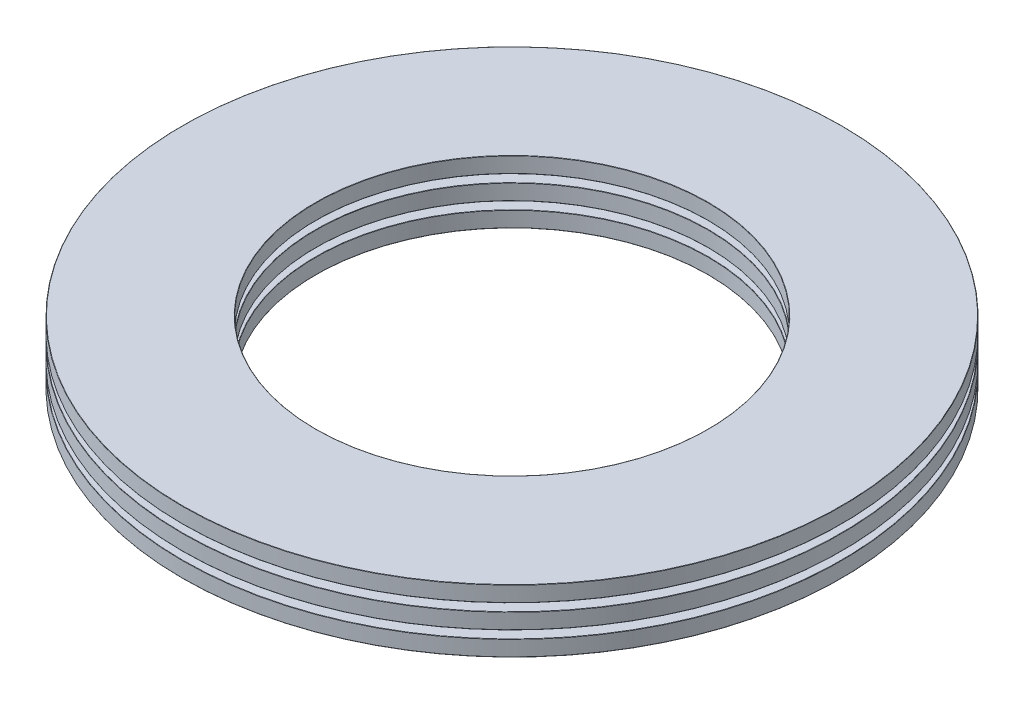
SolidWorks part; units mm, degrees
material "Alloy Steel"
ref_plane "Front Plane" through (0, 0, 0) normal (0, 0, 1) x (1, 0, 0)
ref_plane "Top Plane" through (0, 0, 0) normal (0, 1, 0) x (1, 0, 0)
ref_plane "Right Plane" through (0, 0, 0) normal (1, 0, 0) x (0, 0, -1)
sketch "Sketch1" plane through (0, 0, 0) normal (1, 0, 0) x (0, 0, -1)
  line L0 (-21, 0) -> (21, 0) construction
  line L1 (0, -1) -> (0, 1) construction
  line L2 (-21, 0.5) -> (-12.5, 0.5)
  line L3 (-21, 0.5) -> (-21, -0.5)
  line L4 (-21, -0.5) -> (-12.5, -0.5)
  line L5 (-12.5, 0.5) -> (-12.5, -0.5)
  line L7 (-16.75, 1) -> (-16.75, 0.5) construction
  line L8 (-19.9375, 1) -> (-13.5625, 1) construction
  line L9 (-19.9375, 1) -> (-19.9375, -1) construction
  line L10 (-19.9375, -1) -> (-13.5625, -1) construction
  line L11 (-13.5625, 1) -> (-13.5625, -1) construction
  point P16 (-19.9375, 0)
  dimension "D1" = 6.375
  dimension "OD" = 42
  dimension "Shaft Dia" = 25
  dimension "Th" = 2
  dimension "D2" = 1
  dimension "D3" = 8.5
revolve "Revolve1" add sketch "Sketch1" angle 360 about L1
sketch "Sketch3" plane through (0, 0, 0) normal (1, 0, 0) x (0, 0, -1)
  line L0 (-19.9375, 1) -> (-19.9375, -1) construction
  line L1 (-19.9375, 0) -> (-13.5625, 0)
  line L2 (-19.9375, 0) -> (-19.9375, 1)
  line L3 (-19.9375, 1) -> (-13.5625, 1)
  line L4 (-13.5625, 0) -> (-13.5625, 1)
revolve "Cut-Revolve1" cut sketch "Sketch3" angle 360 about L1
sketch "Sketch2" plane through (0, 0, 0) normal (1, 0, 0) x (0, 0, -1)
  line L1 (-19.9375, 0) -> (-13.5625, 0)
  line L2 (-19.9375, 0) -> (-19.9375, 1)
  line L3 (-19.9375, 1) -> (-13.5625, 1)
  line L4 (-13.5625, 0) -> (-13.5625, 1)
revolve "Revolve2" add sketch "Sketch2" angle 360 about L1
ref_axis "Axis1" through (0, 1, 0) along (0, -1, 0)
pattern_circular "CirPattern1" count 16 over 360 about axis through (0, 1, 0) along (0, -1, 0) of bodies 187 411
pattern_circular "CirPattern2" count 16 every 22.5 about axis through (0, 1, 0) along (0, -1, 0) of "Cut-Revolve1"
sketch "Sketch4" plane through (0, 0, 0) normal (1, 0, 0) x (0, 0, -1)
  line L0 (-21, 0.5) -> (-21, -0.5) construction
  line L1 (-21, 0.999) -> (-12.5, 0.999)
  line L2 (-21, 0.999) -> (-21, 1.999)
  line L3 (-21, 1.999) -> (-12.5, 1.999)
  line L4 (-12.5, 0.999) -> (-12.5, 1.999)
  line L5 (-21, -1.999) -> (-12.5, -1.999)
  line L6 (-21, -1.999) -> (-21, -0.999)
  line L7 (-21, -0.999) -> (-12.5, -0.999)
  line L8 (-12.5, -1.999) -> (-12.5, -0.999)
  line L10 (-12.5, 0.5) -> (-12.5, -0.5) construction
  line L11 (0, 0) -> (-21, 0) construction
  line L12 (-21, 0) -> (21, 0) construction
  line L13 (0, -1) -> (0, 1) construction
  dimension "Ht" = 3.998
  dimension "Washer Th" = 1
  dimension "Washer ID" = 25
  dimension "Washer OD" = 42
revolve "Revolve3" add sketch "Sketch4" angle 360 about L1
fillet "Fillet1" radius 0.02 4 edges at (0, 0.999, -12.5) (0, 1.999, -12.5) (0, 0.999, -21) (0, 1.999, -21)
fillet "Fillet2" radius 0.02 4 edges at (0, -0.5, -12.5) (0, 0.5, -12.5) (0, -0.5, -21) (0, 0.5, -21)
fillet "Fillet3" radius 0.02 4 edges at (0, -1.999, -12.5) (0, -0.999, -12.5) (0, -1.999, -21) (0, -0.999, -21)
equation "\"D2@Sketch1\" = \"Th@Sketch1\"*.5"
equation "\"D1@Fillet1\" = \"Th@Sketch1\"*.01"
equation "\"D1@Fillet2\" = \"D1@Fillet1\""
equation "\"D1@Fillet3\" = \"D1@Fillet1\""
equation "\"D1@Sketch1\" = 6.375"
equation "\"Angle@CirPattern1\" = 360/\"Rollers@CirPattern1\""
equation "\"Rollers@CirPattern1\" = \"OD@Sketch1\"*.375"
equation "\"D1@CirPattern2\" = \"Rollers@CirPattern1\""
equation "\"D2@CirPattern2\" = \"Angle@CirPattern1\""
equation "\"Ht@Sketch4\"=\"Th@Sketch1\"*10mm-0.3150in -0.3150in "
